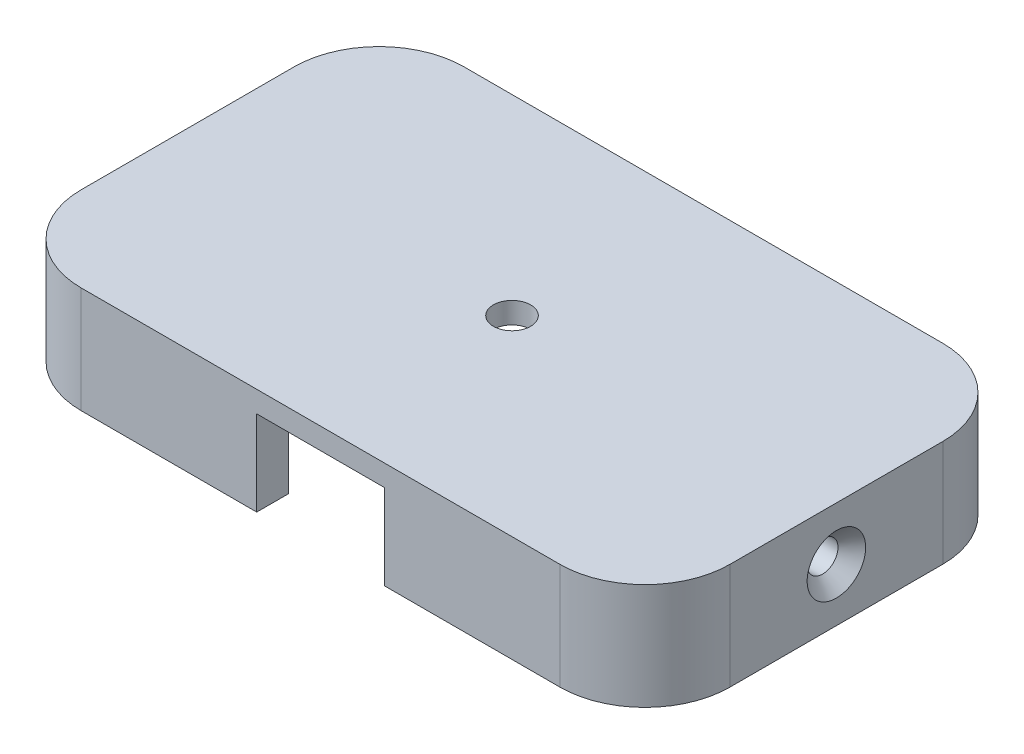
SolidWorks part; units mm, degrees
ref_plane "Front Plane" through (0, 0, 0) normal (0, 0, 1) x (1, 0, 0)
ref_plane "Top Plane" through (0, 0, 0) normal (0, 1, 0) x (1, 0, 0)
ref_plane "Right Plane" through (0, 0, 0) normal (1, 0, 0) x (0, 0, -1)
sketch "Sketch1" plane through (0, 0, 0) normal (0, 1, 0) x (1, 0, 0)
  line L0 (-22.5, 18) -> (22.5, 18)
  line L1 (-22.5, -15) -> (22.5, -15)
  line L2 (-27.5, -10) -> (-27.5, 10)
  line L3 (-22.5, 15) -> (22.5, 15)
  line L4 (27.5, -10) -> (27.5, 10)
  line L5 (-27.5, -15) -> (27.5, 15) construction
  line L6 (-27.5, 15) -> (27.5, -15) construction
  line L7 (30.5, -10) -> (30.5, 10)
  line L8 (-22.5, -18) -> (22.5, -18)
  line L9 (-30.5, -10) -> (-30.5, 10)
  arc A0 (22.5, 15) -> (27.5, 10) centre (22.5, 10) cw
  arc A1 (27.5, -10) -> (22.5, -15) centre (22.5, -10) cw
  arc A2 (-22.5, -15) -> (-27.5, -10) centre (-22.5, -10) cw
  arc A3 (-27.5, 10) -> (-22.5, 15) centre (-22.5, 10) cw
  arc A4 (22.5, 18) -> (30.5, 10) centre (22.5, 10) cw
  arc A5 (30.5, -10) -> (22.5, -18) centre (22.5, -10) cw
  arc A6 (-22.5, -18) -> (-30.5, -10) centre (-22.5, -10) cw
  arc A7 (-30.5, 10) -> (-22.5, 18) centre (-22.5, 10) cw
  point P0 (0, 0)
  dimension "D3" = 5
  dimension "D1" = 55
  dimension "D2" = 30
  dimension "D4" = 3
extrude "Boss-Extrude1" add sketch "Sketch1" against normal blind 10
extrude "Boss-Extrude2" add sketch "Sketch1<2>" against normal blind 2 contours A3 L2 A2 L1 A1 L4 A0 L3 region at (0, 0, 0)
sketch "Sketch1<2>" plane through (0, 0, 0) normal (0, 1, 0) x (1, 0, 0) same geometry as "Sketch1"
hole_wizard "CSK for M2.5 Flat Head Machine Screw1" positions "Sketch2" profile "Sketch4" countersink size "M2.5" standard "ANSI Metric"
sketch "Sketch2" plane through (30.5, 0, 0) normal (1, 0, 0) x (0, 0, -1)
  line L0 (-10, 0) -> (10, -10) construction
  point P6 (0, -5)
sketch "Sketch4" plane through (30.5, -5, 0) normal (0, 1, 0) x (0, 0, -1)
  line L0 (0, 0) -> (0, 10.8712)
  line L1 (0, 10.8712) -> (1.45, 10)
  line L2 (1.45, 10) -> (1.45, 1.3)
  line L3 (1.45, 1.3) -> (2.75, 0)
  line L5 (2.75, 0) -> (0, 0)
  line L6 (-1.45, 1.3) -> (-2.75, 0) construction
  line L10 (0, 10.8712) -> (-1.45, 10) construction
  line L11 (0, -6.35) -> (0, 107.95) construction
  dimension "Hole Dia." = 2.9
  dimension "Hole Depth" = 10
  dimension "Near C'Sink Dia." = 5.5
  dimension "Near C'Sink Angle" = 90
  dimension "Drill Angle" = 118
mirror "Mirror1" about plane through (0, 0, 0) normal (1, 0, 0) of "CSK for M2.5 Flat Head Machine Screw1"
hole_wizard "Ø3.5 (3.5) Diameter Hole1" positions "Sketch6" profile "Sketch7" hole size "Ø3.5" standard "ANSI Metric" end condition through all
sketch "Sketch6" plane through (0, -2, 0) normal (0, -1, 0) x (-1, 0, 0)
  point P0 (0, 0)
sketch "Sketch7" plane through (0, -2, 0) normal (1, 0, 0) x (0, 0, -1)
  line L0 (0, 0) -> (0, 2)
  line L1 (0, 2) -> (1.75, 2)
  line L2 (1.75, 2) -> (1.75, 0)
  line L5 (1.75, 0) -> (0, 0)
  line L11 (0, -6.35) -> (0, 107.95) construction
  dimension "Thru Hole Dia." = 3.5
  dimension "Thru Hole Depth" = 2
sketch "Sketch8" plane through (0, 0, 18) normal (0, 0, 1) x (1, 0, 0)
  line L0 (-22.5, -10) -> (22.5, -10) construction
  line L1 (6, -2) -> (-6, -2)
  line L2 (6, -2) -> (6, -10)
  line L3 (6, -10) -> (-6, -10)
  line L4 (-6, -2) -> (-6, -10)
  line L5 (6, -2) -> (-6, -10) construction
  line L6 (6, -10) -> (-6, -2) construction
  line L7 (0, 0) -> (0, -6) construction
  line L8 (-22.5, 0) -> (22.5, 0) construction
  point P0 (0, -6)
  dimension "D1" = 12
  dimension "D2" = 8
extrude "Cut-Extrude1" cut sketch "Sketch8" against normal blind 5
sketch "Sketch9" plane through (27.5, 0, 0) normal (-1, 0, 0) x (0, 0, 1)
  line L0 (10, -2) -> (-10, -2) construction
  line L1 (2.7713, -5) -> (1.3856, -2.6)
  line L2 (1.3856, -2.6) -> (-1.3856, -2.6)
  line L3 (-1.3856, -2.6) -> (-2.7713, -5)
  line L4 (-2.7713, -5) -> (-1.3856, -7.4)
  line L5 (-1.3856, -7.4) -> (1.3856, -7.4)
  line L6 (1.3856, -7.4) -> (2.7713, -5)
  line L7 (-4, -10) -> (-4, -2)
  line L8 (-4, -2) -> (4, -2)
  line L9 (0, -2) -> (0, -5) construction
  line L10 (4, -10) -> (4, -2)
  line L11 (10, -10) -> (-10, -10) construction
  line L12 (-4, -10) -> (4, -10)
  circle A0 centre (0, -5) radius 2.4 construction
  circle A2 centre (0, -5) radius 1.45
  circle A3 centre (0, -5) radius 1.45 construction
  line M5 (10, -2) -> (-10, -2)
  line M7 (-10, -10) -> (10, -10)
  dimension "D1" = 4.8
  dimension "D2" = 8
extrude "Boss-Extrude3" [suppressed] add sketch "Sketch9" along normal blind 2 contours L10 L7 L6 L5 L4 L3 L2 L1 M7 M5
mirror "Mirror2" [suppressed] about plane through (0, 0, 0) normal (1, 0, 0)
